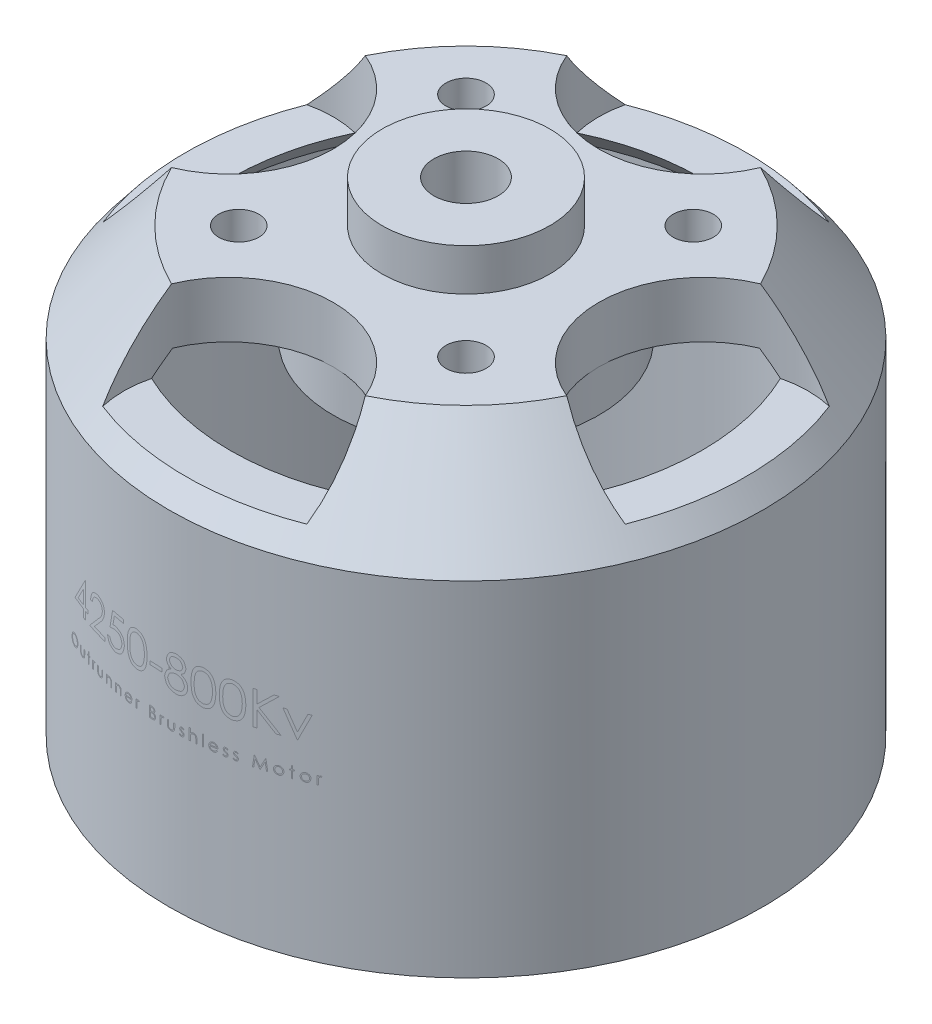
SolidWorks part; units mm, degrees
material "Ductile Iron"
ref_plane "Front Plane" through (0, 0, 0) normal (0, 0, 1) x (1, 0, 0)
ref_plane "Top Plane" through (0, 0, 0) normal (0, 1, 0) x (1, 0, 0)
ref_plane "Right Plane" through (0, 0, 0) normal (1, 0, 0) x (0, 0, -1)
sketch "Sketch1" plane through (0, 0, 0) normal (0, 1, 0) x (1, 0, 0)
  circle A0 centre (0, 0) radius 21.25
  dimension "D1" = 42.5
extrude "Boss-Extrude1" add sketch "Sketch1" along normal blind 24.5 contours A0
sketch "Sketch2" plane through (0, 24.5, 0) normal (0, 1, 0) x (1, 0, 0)
  circle A0 centre (0, 0) radius 19.25
  circle A1 centre (0, 0) radius 21.25 construction
  dimension "D1" = 2
extrude "Cut-Extrude1" cut sketch "Sketch2" against normal through all
sketch "Sketch3" plane through (0, 0, 0) normal (0, 0, 1) x (1, 0, 0)
  line L0 (-10, 13.5) -> (10, 13.5) construction
  line L1 (19.25, 24.5) -> (-19.25, 24.5) construction
  line L2 (-10, 11) -> (10, 11) construction
  text T0 "4250-800Kv" font "Century Gothic" height in points 9
  text T1 "Outrunner Brushless Motor" font "Century Gothic" height in points 3
  dimension "D1" = 20
  dimension "D2" = 10
  dimension "D3" = 11
  dimension "D4" = 11
wrap "Wrap1" sketch "Sketch3" wrap type scribe source sketch "Sketch3"
sketch "Sketch4" plane through (0, 24.5, 0) normal (0, 1, 0) x (1, 0, 0)
  circle A0 centre (0, 0) radius 19.25 construction
  circle A1 centre (0, 0) radius 21.25 construction
  circle A2 centre (0, 0) radius 19.25
  circle A3 centre (0, 0) radius 21.25
extrude "Boss-Extrude2" add sketch "Sketch4" along normal blind 0.1
sketch "Sketch7" plane through (0, 0, 0) normal (0, 0, 1) x (1, 0, 0)
  line L0 (-21.25, 24.6) -> (-15.75, 31.6)
  line L1 (-15.75, 31.6) -> (0, 31.6)
  line L2 (-15.6929, 27.6) -> (0, 27.6)
  line L3 (-15.6929, 27.6) -> (-18.05, 24.6)
  line L4 (19.25, 24.6) -> (-19.25, 24.6) construction
  line L5 (0, 31.6) -> (0, 27.6)
  line L6 (-21.25, 24.6) -> (-18.05, 24.6)
  dimension "D1" = 7
  dimension "D2" = 5.5
  dimension "D3" = 4
  dimension "D4" = 3.2
revolve "Revolve1" add sketch "Sketch7" angle 360 about L5
sketch "Sketch8" plane through (0, 31.6, 0) normal (0, 1, 0) x (1, 0, 0)
  line L0 (0, -9.5) -> (0, 9.5)
  line L1 (-9.5, 0) -> (9.5, 0)
  circle A0 centre (17, 0) radius 7.5
  circle A1 centre (0, -17) radius 7.5
  circle A2 centre (-17, 0) radius 7.5
  circle A3 centre (0, 17) radius 7.5
  point P4 (0, 0)
  point P8 (0, 0)
  point P19 (0, 0)
  circle M7 centre (0, 0) radius 15.75
  dimension "D2" = 15
  dimension "D1" = 19
  dimension "D3" = 4
extrude "Cut-Extrude2" cut sketch "Sketch8" against normal blind 5.5 contours A2 M7 | A2 M7 | A3 M7 | A3 M7 | A0 M7 | A0 M7 | A1 M7 | A1 M7 region at (0, 31.6, 12.8504) region at (0, 31.6, 19.219) region at (0, 31.6, -12.8504) region at (-12.8504, 31.6, 0) region at (12.8504, 31.6, 0) region at (19.219, 31.6, 0) region at (-19.219, 31.6, 0) region at (0, 31.6, -19.219)
sketch "Sketch9" plane through (0, 31.6, 0) normal (0, 1, 0) x (1, 0, 0)
  circle A0 centre (0, 0) radius 6
  dimension "D1" = 12
extrude "Boss-Extrude3" add sketch "Sketch9" along normal blind 3
sketch "Sketch13" plane through (0, 27.6, 0) normal (0, -1, 0) x (1, 0, 0)
  circle A0 centre (0, 0) radius 9.5
  arc A1 (-6.9119, 14.0887) -> (6.9119, 14.0887) centre (0, 17) ccw construction
extrude "Boss-Extrude6" add sketch "Sketch13" along normal blind 3
sketch "Sketch10" plane through (0, 34.6, 0) normal (0, 1, 0) x (1, 0, 0)
  circle A0 centre (0, 0) radius 2.3
  dimension "D1" = 4.6
extrude "Cut-Extrude4" cut sketch "Sketch10" against normal up to surface (10 mm away) up to face at (0, 24.6, -9.5)
hole_wizard "#33 (0.113) Diameter Hole1" positions "Sketch17" profile "Sketch16" hole size "#33" standard "ANSI Inch" end condition through all
sketch "Sketch17" plane through (0, 31.6, 0) normal (0, 1, 0) x (1, 0, 0)
  line L0 (-8.1317, -8.1317) -> (8.1317, 8.1317) construction
  line L2 (-8.1317, 8.1317) -> (8.1317, -8.1317) construction
  point P0 (-8.1317, -8.1317)
  point P2 (-8.1317, 8.1317)
  point P4 (8.1317, 8.1317)
  point P6 (8.1317, -8.1317)
  dimension "D1" = 11.5
  dimension "D2" = 90
  dimension "D3" = 11.5
sketch "Sketch16" plane through (-8.1317, 31.6, 8.1317) normal (1, 0, 0) x (0, 0, 1)
  line L0 (0, 0) -> (0, 31.6)
  line L1 (0, 31.6) -> (1.4351, 31.6)
  line L2 (1.4351, 31.6) -> (1.4351, 0)
  line L5 (1.4351, 0) -> (0, 0)
  line L11 (0, -6.35) -> (0, 107.95) construction
  dimension "Thru Hole Dia." = 2.8702
  dimension "Thru Hole Depth" = 31.6
